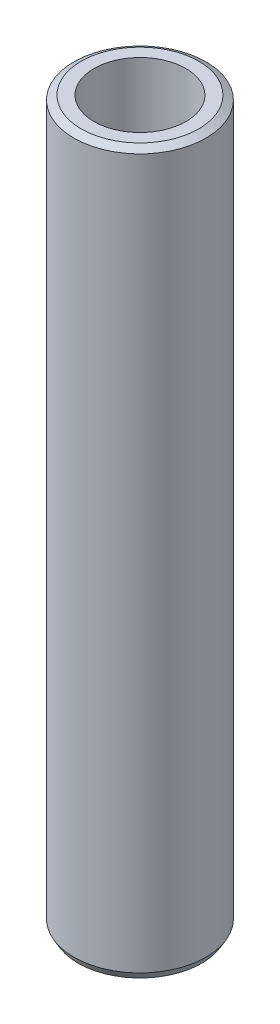
SolidWorks part; units mm, degrees
ref_plane "Front Plane" through (0, 0, 0) normal (0, 0, 1) x (1, 0, 0)
ref_plane "Top Plane" through (0, 0, 0) normal (0, 1, 0) x (1, 0, 0)
ref_plane "Right Plane" through (0, 0, 0) normal (1, 0, 0) x (0, 0, -1)
sketch "Sketch1" plane through (0, 0, 0) normal (0, 1, 0) x (1, 0, 0)
  circle A0 centre (0, 0) radius 55
  dimension "SHAFT_OD" = 110
extrude "Boss-Extrude1" add sketch "Sketch1" along normal blind 600
sketch "Sketch2" plane through (0, 0, 0) normal (0, 1, 0) x (1, 0, 0)
  circle A0 centre (0, 0) radius 38.2659
  dimension "BORE_D" = 76.5319
extrude "Cut-Extrude1" cut sketch "Sketch2" along normal through all
chamfer "Chamfer1" distance 3.5457 angle 60 2 edges at (0, 600, 55) (0, 0, 55) first distance on face at (0, 600, 55) first distance on face at (0, 0, 38.2659)
